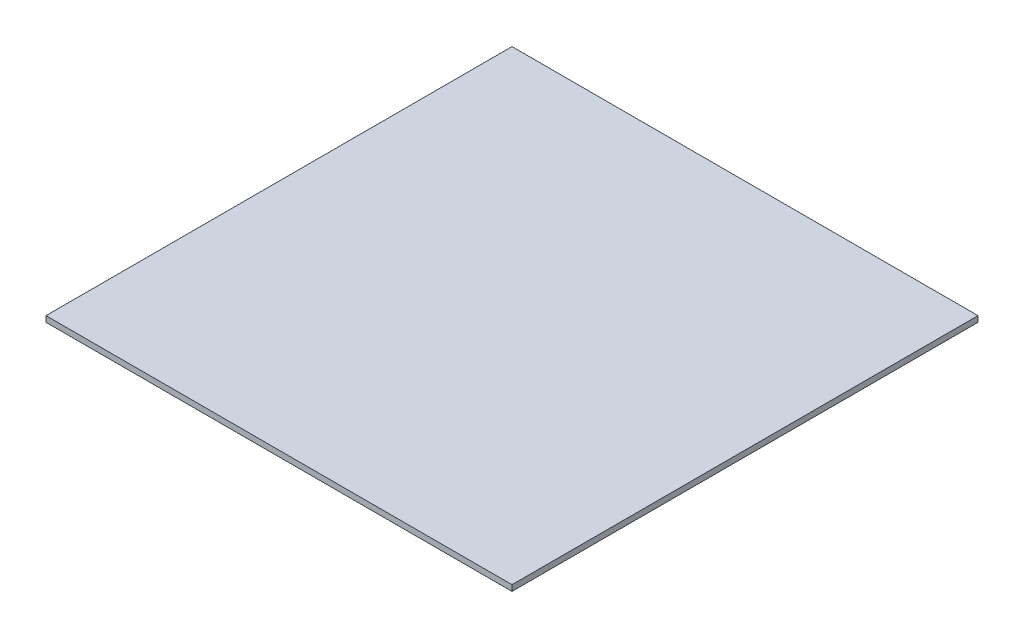
SolidWorks part; units mm, degrees
ref_plane "Front" through (0, 0, 0) normal (0, 0, 1) x (1, 0, 0)
ref_plane "Top" through (0, 0, 0) normal (0, 1, 0) x (1, 0, 0)
ref_plane "Right" through (0, 0, 0) normal (1, 0, 0) x (0, 0, -1)
sketch "Эскиз1" plane through (0, 0, 0) normal (0, 1, 0) x (1, 0, 0)
  line L1 (-160, -160) -> (160, -160)
  line L2 (-160, -160) -> (-160, 160)
  line L3 (-160, 160) -> (160, 160)
  line L4 (160, -160) -> (160, 160)
  line L5 (-160, -160) -> (160, 160) construction
  line L6 (-160, 160) -> (160, -160) construction
  point P0 (0, 0)
  dimension "D1" = 320
  dimension "D2" = 320
extrude "Бобышка-Вытянуть1" add sketch "Эскиз1" along normal blind 4
